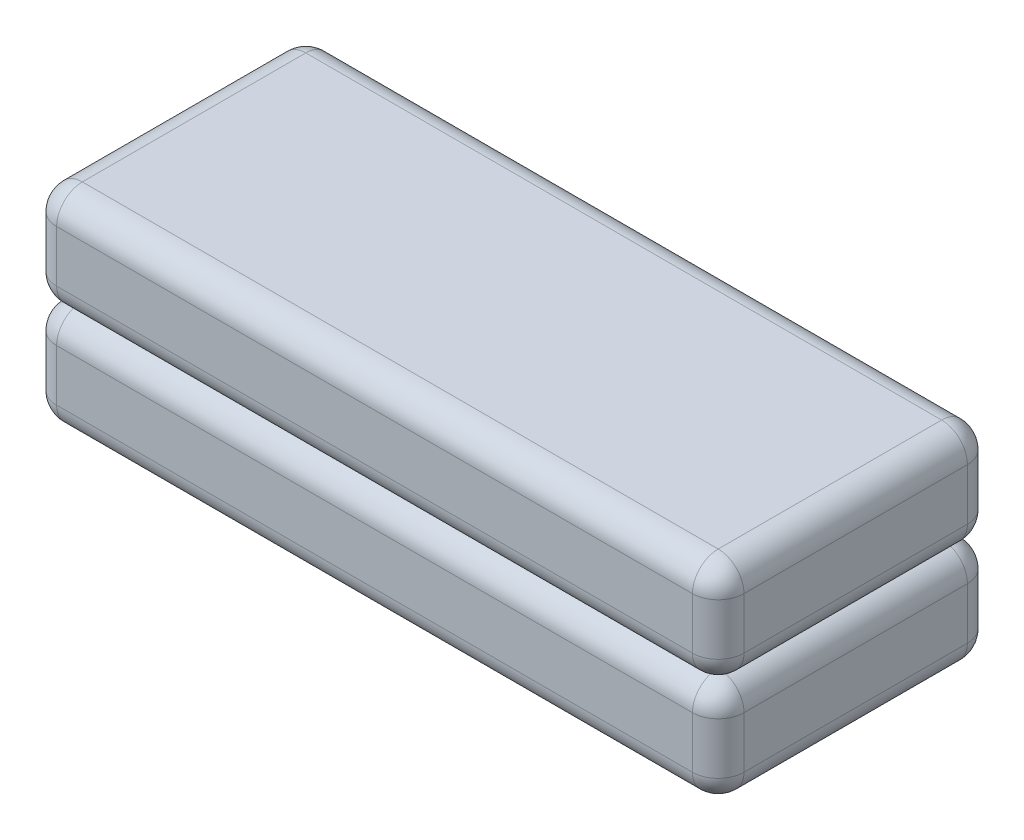
SolidWorks part; units mm, degrees
ref_plane "Front Plane" through (0, 0, 0) normal (0, 0, 1) x (1, 0, 0)
ref_plane "Top Plane" through (0, 0, 0) normal (0, 1, 0) x (1, 0, 0)
ref_plane "Right Plane" through (0, 0, 0) normal (1, 0, 0) x (0, 0, -1)
sketch "Sketch1" plane through (0, 0, 0) normal (0, 1, 0) x (1, 0, 0)
  line L1 (1000, -400) -> (-1000, -400)
  line L2 (1000, -400) -> (1000, 400)
  line L3 (1000, 400) -> (-1000, 400)
  line L4 (-1000, -400) -> (-1000, 400)
  line L5 (1000, -400) -> (-1000, 400) construction
  line L6 (1000, 400) -> (-1000, -400) construction
  point P0 (0, 0)
  dimension "D1" = 800
  dimension "D2" = 2000
extrude "Boss-Extrude1" add sketch "Sketch1" along normal blind 300
fillet "Fillet1" radius 75 12 edges at (0, 300, 400) (-1000, 300, 0) (-1000, 150, 400) (1000, 150, 400) (1000, 300, 0) (0, 0, 400) (1000, 0, 0) (-1000, 0, 0) (1000, 150, -400) (0, 300, -400) (-1000, 150, -400) (0, 0, -400)
sketch "Sketch2" plane through (0, 0, 0) normal (0, -1, 0) x (1, 0, 0)
  line L1 (-1000, -400) -> (1000, -400)
  line L2 (-1000, -400) -> (-1000, 400)
  line L3 (-1000, 400) -> (1000, 400)
  line L4 (1000, -400) -> (1000, 400)
  line L5 (-1000, -400) -> (1000, 400) construction
  line L6 (-1000, 400) -> (1000, -400) construction
  point P0 (0, 0)
  dimension "D1" = 800
  dimension "D2" = 2000
extrude "Boss-Extrude2" add sketch "Sketch2" along normal blind 300
fillet "Fillet4" radius 75 12 edges at (-1000, -300, 0) (-1000, 0, 0) (-1000, -150, -400) (0, -300, -400) (0, 0, -400) (1000, -150, -400) (1000, -300, 0) (1000, 0, 0) (1000, -150, 400) (0, -300, 400) (-1000, -150, 400) (0, 0, 400)
sketch "Sketch3" plane through (0, -300, 0) normal (0, -1, 0) x (1, 0, 0)
  line L2 (-984.0971, 0) -> (1054.2379, 0) construction
  line L3 (0, 466.5428) -> (0, -449.539) construction
  line L4 (-775, 530.3072) -> (-775, -521.8053) construction
  line L5 (-925, 325) -> (-925, -325) construction
  line L6 (-1158.1059, 225) -> (1112.6274, 225) construction
  line L7 (925, 325) -> (-925, 325) construction
  circle A0 centre (-775, 225) radius 50
  circle A1 centre (775, 225) radius 50
  circle A2 centre (775, -225) radius 50
  circle A3 centre (-775, -225) radius 50
  point P15 (0, 0)
  dimension "D1" = 150
  dimension "D3" = 100
  dimension "D2" = 100
extrude "Cut-Extrude1" cut sketch "Sketch3" against normal blind 5
